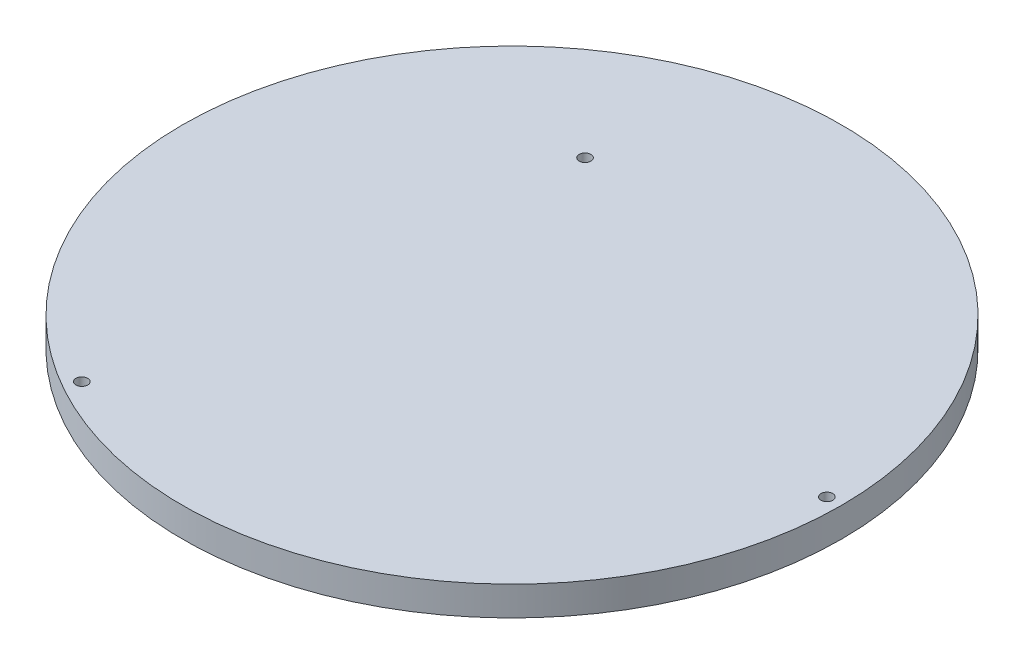
SolidWorks part; units mm, degrees
ref_plane "Front Plane" through (0, 0, 0) normal (0, 0, 1) x (1, 0, 0)
ref_plane "Top Plane" through (0, 0, 0) normal (0, 1, 0) x (1, 0, 0)
ref_plane "Right Plane" through (0, 0, 0) normal (1, 0, 0) x (0, 0, -1)
sketch "Sketch1" plane through (0, 0, 0) normal (0, 0, 1) x (1, 0, 0)
  line L0 (0, -200000) -> (0, 218797.9879) construction
  line L1 (142.875, -24.4122) -> (142.875, -37.1122) construction
  line L2 (0, -24.4122) -> (142.875, -24.4122) construction
  line L3 (142.875, -37.1122) -> (0, -37.1122) construction
  line L4 (0, -200000) -> (0, 218797.9879) construction
  line L5 (142.875, -24.4122) -> (142.875, -37.1122)
  line L6 (0, -24.4122) -> (142.875, -24.4122)
  line L7 (142.875, -37.1122) -> (0, -37.1122)
  line L8 (0, -24.4122) -> (0, -37.1122)
revolve "Revolve1" add sketch "Sketch1" angle 360 about L4
hole_wizard "1/4-20 Tapped Hole1" positions "Sketch2" profile "Sketch3" tap size "1/4-20" standard "ANSI Inch" end condition up to next
sketch "Sketch2" plane through (0, -24.4122, 0) normal (0, 1, 0) x (1, 0, 0)
  line L0 (0, 0) -> (136.525, 0) construction
  line L3 (0, 0) -> (-68.2625, -118.2341) construction
  line L6 (0, 0) -> (-43.2486, 74.9088) construction
  circle A0 centre (0, 0) radius 136.525
  point P0 (136.525, 0)
  point P2 (-68.2625, -118.2341)
  point P4 (-43.2486, 74.9088)
  dimension "D1" = 120
  dimension "D2" = 120
sketch "Sketch3" plane through (136.525, -24.4122, 0) normal (1, 0, 0) x (0, 0, 1)
  line L0 (0, 0) -> (0, 12.7)
  line L1 (0, 12.7) -> (2.5527, 12.7)
  line L2 (2.5527, 12.7) -> (2.5527, 0)
  line L5 (2.5527, 0) -> (0, 0)
  line L11 (0, -6.35) -> (0, 107.95) construction
  dimension "Thru Tap Drill Dia." = 5.1054
  dimension "Thru Tap Drill Depth" = 12.7
cosmetic thread "Hole Thread1"
cosmetic thread "Hole Thread2"
cosmetic thread "Hole Thread3"
